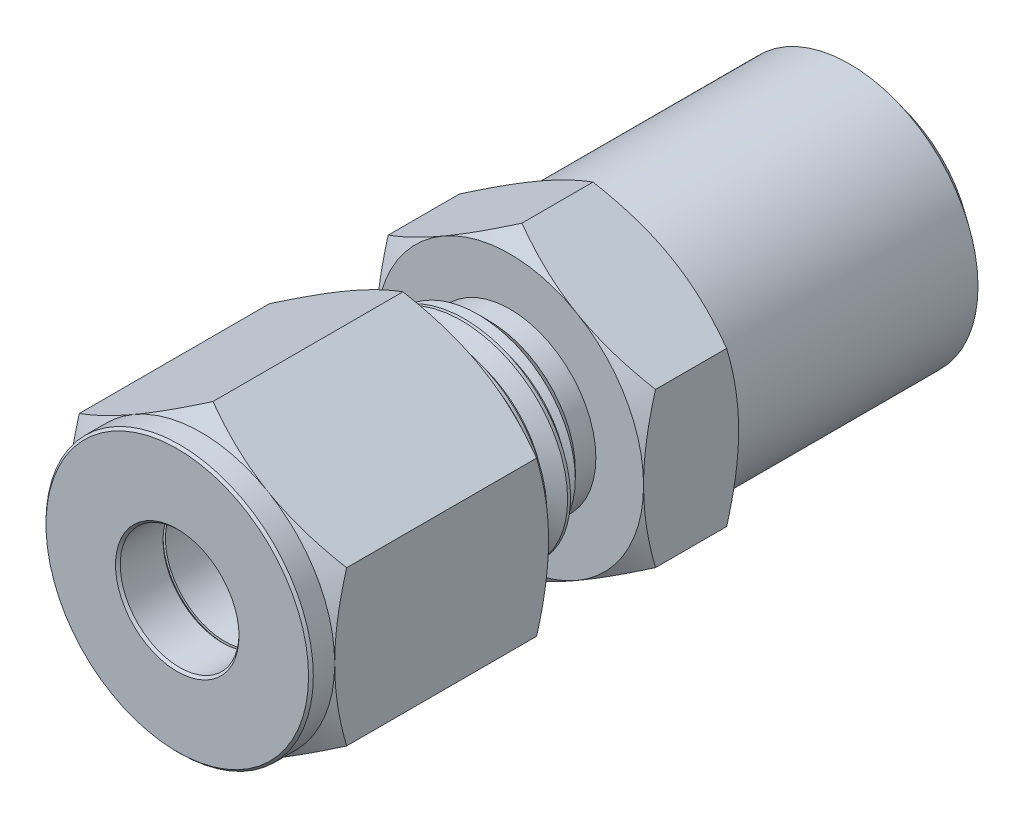
SolidWorks part; units mm, degrees
ref_plane "Front Plane" through (0, 0, 0) normal (0, 0, 1) x (1, 0, 0)
ref_plane "Top Plane" through (0, 0, 0) normal (0, 1, 0) x (1, 0, 0)
ref_plane "Right Plane" through (0, 0, 0) normal (1, 0, 0) x (0, 0, -1)
sketch "Sketch1" plane through (0, 0, 0) normal (1, 0, 0) x (0, 0, -1)
  line L0 (0, 0) -> (37.084, 0) construction
  line L1 (0, 3.175) -> (0, -3.175) construction
  line L2 (12.7, 7.1437) -> (12.7, -7.1437) construction
  line L3 (5.08, 5.5562) -> (5.08, -5.5562) construction
  line L4 (5.08, 5.5562) -> (5.08, 4.2862) construction
  line L5 (22.86, 7.1437) -> (22.86, -7.1437) construction
  line L6 (4.445, 4.699) -> (9.3218, 3.6068) construction
  line L7 (9.3218, 3.6068) -> (9.3218, 3.175) construction
  line L8 (9.3218, 3.175) -> (5.1308, 3.175) construction
  line L9 (5.1308, 3.175) -> (4.445, 3.8608) construction
  line L10 (4.445, 3.8608) -> (4.445, 4.699) construction
  line L11 (2.54, 4.6609) -> (3.556, 4.6609) construction
  line L12 (3.556, 4.6609) -> (3.556, 3.8608) construction
  line L13 (3.556, 3.8608) -> (4.445, 3.8608) construction
  line L14 (22.86, 2.3749) -> (22.86, -2.3749) construction
  line L15 (4.445, 3.8608) -> (4.445, 3.175) construction
  line L16 (5.1308, 3.175) -> (2.54, 3.175) construction
  line L17 (2.54, 3.175) -> (2.54, 4.6609) construction
  line L18 (4.445, 3.175) -> (5.1308, 3.175) construction
  line L19 (0, 3.175) -> (2.54, 3.175) construction
  line L20 (2.54, 3.175) -> (5.08, 3.175) construction
  line L21 (37.084, 6.858) -> (37.084, -6.858) construction
  line L26 (37.084, 4.6228) -> (37.084, -4.6228) construction
  point P4 (1.27, 0)
  point P10 (5.08, 0)
  point P12 (12.7, 0)
  point P15 (17.78, 0)
  point P16 (7.366, 0)
  point P17 (15.24, 0)
  point P33 (22.86, 0)
  dimension "R" = 14.224
sketch "Sketch2" plane through (0, 0, 0) normal (0, 0, 1) x (1, 0, 0)
  line L0 (0, 3.175) -> (0, -3.175) construction
  line L1 (0, 8.2489) -> (-7.1437, 4.1244)
  line L2 (-7.1437, 4.1244) -> (-7.1438, -4.1244)
  line L3 (-7.1438, -4.1244) -> (0, -8.2489)
  line L4 (0, -8.2489) -> (7.1437, -4.1244)
  line L5 (7.1437, -4.1244) -> (7.1438, 4.1244)
  line L6 (7.1438, 4.1244) -> (0, 8.2489)
  line L7 (0, 8.2489) -> (0, 0) construction
  circle A0 centre (0, 0) radius 7.1438 construction
extrude "Boss-Extrude1" add sketch "Sketch2" against normal up to vertex (12.7 mm away) up to point (0, 0, -12.7)
sketch "Sketch3" plane through (0, 0, 0) normal (1, 0, 0) x (0, 0, -1)
  line L0 (0, 8.2489) -> (0, 7.1437)
  line L1 (0, 4.1244) -> (0, 8.2489) construction
  line L2 (0, 7.1437) -> (1.27, 7.1437)
  line L3 (1.27, 7.1437) -> (1.9081, 8.2489)
  line L4 (12.7, 8.2489) -> (0, 8.2489) construction
  line L5 (1.9081, 8.2489) -> (12.0619, 8.2489)
  line L6 (12.0619, 8.2489) -> (12.7, 7.1437)
  line L7 (12.7, 7.1437) -> (12.7, 8.2489)
  line L8 (12.7, 8.2489) -> (12.7, 9.354)
  line L9 (12.7, 9.354) -> (0, 9.354)
  line L10 (0, 9.354) -> (0, 8.2489)
  line L11 (0, 3.175) -> (0, 0)
  line L12 (0, 3.175) -> (0, -3.175) construction
  line L13 (0, 0) -> (12.7, 0)
  line L14 (12.7, 7.1437) -> (12.7, -7.1437) construction
  line L15 (12.7, 0) -> (12.7, 5.5562)
  line L16 (12.7, 5.5562) -> (5.08, 5.5562)
  line L17 (5.08, 5.5562) -> (5.08, 4.2862) construction
  line L18 (5.08, 4.2862) -> (2.54, 4.2862) construction
  line L19 (2.54, 4.2862) -> (2.54, 3.175)
  line L20 (2.54, 3.175) -> (0, 3.175)
  line L21 (2.54, 4.2862) -> (2.54, 5.5562) construction
  line L22 (2.54, 5.5562) -> (5.08, 5.5562) construction
  line L23 (5.08, 4.9212) -> (2.54, 4.9213)
  line L24 (2.54, 4.9213) -> (2.54, 4.2862)
  line L25 (5.08, 4.9212) -> (5.08, 5.5562)
  dimension "D1" = 30
  dimension "D2" = 1.27
revolve "Cut-Revolve1" cut sketch "Sketch3" angle 360 about L0
chamfer "Chamfer1" distance 0.127 angle 45 3 edges at (3.175, 0, 0) (3.175, 0, -2.54) (7.1437, 0, 0)
sketch "Sketch4" plane through (0, 0, 0) normal (1, 0, 0) x (0, 0, -1)
  line L1 (17.78, 0) -> (7.366, 0)
  line L2 (17.78, 0) -> (17.78, 5.5563)
  line L3 (17.78, 5.5563) -> (7.366, 5.5562)
  line L4 (7.366, 0) -> (7.366, 5.5562)
  dimension "D1" = 10.414
revolve "Revolve1" add sketch "Sketch4" angle 360 about L1
sketch "Sketch5" plane through (0, 0, -7.366) normal (0, 0, -1) x (-1, 0, 0)
  circle A0 centre (0, 0) radius 5.5562 construction
  circle A1 centre (0, 0) radius 5.5562
  point P3 (0, 5.5562)
curve "Helix/Spiral1" pitch 1.27 height 11.684 turns 9.2
sketch "Sketch6" plane through (0, 0, 0) normal (1, 0, 0) x (0, 0, -1)
  line L0 (6.1754, 5.6937) -> (7.4454, 5.6937) construction
  line L1 (7.4454, 5.6937) -> (6.8104, 4.5939) construction
  line L2 (6.8104, 4.5939) -> (6.1754, 5.6937) construction
  line L3 (6.731, 4.7314) -> (6.8898, 4.7314) construction
  line L4 (6.2548, 5.5563) -> (7.366, 5.5563) construction
  line L5 (6.8104, 4.5939) -> (6.8104, 4.7314) construction
  line L6 (6.8104, 5.5563) -> (6.8104, 5.6937) construction
  line L7 (6.731, 4.7314) -> (6.2151, 5.625)
  line L8 (6.2151, 5.625) -> (7.4057, 5.625)
  line L9 (7.4057, 5.625) -> (6.8898, 4.7314)
  line L10 (6.8898, 4.7314) -> (6.731, 4.7314)
  point P10 (6.8104, 5.625)
  dimension "D1" = 1.27
  dimension "D2" = 0.1588
sweep "Cut-Sweep1" cut profiles "Sketch6" path "Helix/Spiral1"
sketch "Sketch7" plane through (0, 0, -17.78) normal (0, 0, -1) x (-1, 0, 0)
  line L0 (0, 0) -> (0, 8.2489) construction
  line L1 (0, 8.2489) -> (-7.1438, 4.1244)
  line L2 (-7.1438, 4.1244) -> (-7.1438, -4.1244)
  line L3 (-7.1438, -4.1244) -> (0, -8.2489)
  line L4 (0, -8.2489) -> (7.1438, -4.1244)
  line L5 (7.1438, -4.1244) -> (7.1438, 4.1244)
  line L6 (7.1438, 4.1244) -> (0, 8.2489)
  circle A0 centre (0, 0) radius 7.1438 construction
extrude "Boss-Extrude2" add sketch "Sketch7" along normal up to vertex (5.08 mm away) up to point (0, 0, -22.86)
sketch "Sketch8" plane through (0, 0, 0) normal (1, 0, 0) x (0, 0, -1)
  line L0 (7.366, 5.6937) -> (7.366, 4.5939)
  line L1 (7.366, 4.5939) -> (8.4659, 5.6937)
  line L2 (8.4659, 5.6937) -> (7.366, 5.6937)
  line L3 (17.78, 5.6937) -> (15.5803, 5.6937)
  line L4 (15.5803, 5.6937) -> (16.6801, 4.5939)
  line L5 (16.6801, 4.5939) -> (17.78, 4.5939)
  line L6 (17.78, 4.5939) -> (17.78, 5.6937)
  line L7 (17.78, 7.1438) -> (18.4181, 8.2489)
  line L9 (22.86, 8.2489) -> (17.78, 8.2489) construction
  line L10 (18.4181, 8.2489) -> (22.2219, 8.2489)
  line L11 (15.24, 2.3749) -> (22.86, 2.3749)
  line L12 (22.2219, 8.2489) -> (22.86, 7.1437)
  line L14 (22.86, 8.2489) -> (22.86, 9.354)
  line L15 (22.86, 9.354) -> (17.78, 9.354)
  line L16 (17.78, 9.354) -> (17.78, 8.2489)
  line L17 (17.78, 8.2489) -> (17.78, 7.1438)
  line L18 (6.8104, 4.5939) -> (7.366, 4.5939) construction
  line L19 (7.4454, 5.6937) -> (7.366, 5.6937) construction
  line L20 (8.4659, 5.6937) -> (15.5803, 5.6937) construction
  line L21 (16.6801, 4.5939) -> (7.366, 4.5939) construction
  line L22 (7.366, 4.0448) -> (11.2498, 3.175)
  line L23 (22.86, 7.1437) -> (22.86, 8.2489)
  line L24 (7.366, 3.9289) -> (7.366, -4.7433) construction
  line L25 (4.445, 4.699) -> (9.3218, 3.6068) construction
  line L26 (22.86, 0) -> (7.366, 0)
  line L27 (7.366, 0) -> (7.366, 4.0448)
  line L28 (11.2498, 3.175) -> (15.24, 3.175)
  line L29 (15.24, 3.175) -> (15.24, 2.3749)
  line L30 (22.86, 2.3749) -> (22.86, 0)
  line L31 (15.24, 0) -> (15.24, 2.3749) construction
  dimension "D1" = 30
revolve "Cut-Revolve2" cut sketch "Sketch8" angle 360 about L0
sketch "Sketch9" plane through (0, 0, 0) normal (1, 0, 0) x (0, 0, -1)
  line L0 (4.445, 4.699) -> (4.445, 3.8608)
  line L1 (4.445, 3.8608) -> (5.1308, 3.175)
  line L2 (5.1308, 3.175) -> (9.3218, 3.175)
  line L3 (9.3218, 3.175) -> (9.3218, 3.6068)
  line L4 (9.3218, 3.6068) -> (4.445, 4.699)
revolve "Revolve2" add sketch "Sketch9" angle 360 about L0
sketch "Sketch10" plane through (0, 0, 0) normal (1, 0, 0) x (0, 0, -1)
  line L0 (2.54, 4.6609) -> (3.556, 4.6609)
  line L1 (3.556, 4.6609) -> (3.556, 3.8608)
  line L2 (3.556, 3.8608) -> (4.445, 3.8608)
  line L4 (4.445, 3.8608) -> (5.1308, 3.175)
  line L5 (5.1308, 3.175) -> (2.54, 3.175)
  line L6 (2.54, 3.175) -> (2.54, 4.6609)
revolve "Revolve3" add sketch "Sketch10" angle 360 about L0
sketch "Sketch11" plane through (0, 0, 0) normal (1, 0, 0) x (0, 0, -1)
  line L0 (22.86, 0) -> (37.084, 0)
  line L1 (37.084, 0) -> (37.084, 6.858)
  line L2 (37.084, 6.858) -> (22.86, 6.858)
  line L3 (22.86, 6.858) -> (22.86, 0)
  line L4 (22.86, 7.1437) -> (22.86, -7.1437) construction
revolve "Revolve4" add sketch "Sketch11" angle 360 about L0
sketch "Sketch14" plane through (0, 0, 0) normal (1, 0, 0) x (0, 0, -1)
  line L0 (37.084, 6.858) -> (37.084, 6.1129) construction
  line L1 (37.084, 6.1129) -> (37.084, 5.3679) construction
  line L2 (37.084, 5.3679) -> (37.084, 4.6228) construction
  line L5 (37.084, 6.858) -> (37.084, -6.858) construction
  line L6 (37.084, 5.3679) -> (35.9406, 6.858)
  line L7 (35.9406, 6.858) -> (37.084, 6.858)
  line L8 (37.084, 6.858) -> (37.084, 5.3679)
  line L10 (37.084, 4.6228) -> (22.86, 4.6228)
  line L11 (22.86, 4.6228) -> (22.86, 0) construction
  line L12 (20.0823, 0) -> (37.084, 0)
  line L13 (20.0823, 0) -> (22.86, 4.6228)
  line L14 (37.084, 0) -> (37.084, 4.6228)
  dimension "D1" = 59
  dimension "D2" = 37.5
revolve "Cut-Revolve4" cut sketch "Sketch14" angle 360 about L0
equation "\"D4@Helix/Spiral1\" = \"Straight Thread Pitch@Sketch1\""
equation "\"D3@Helix/Spiral1\" = \"D4@Helix/Spiral1\" + \"D1@Sketch4\""
equation "\"D1@Sketch6\" = \"D4@Helix/Spiral1\""
equation "\"D2@Sketch6\" = \"D1@Sketch6\" / 8"
